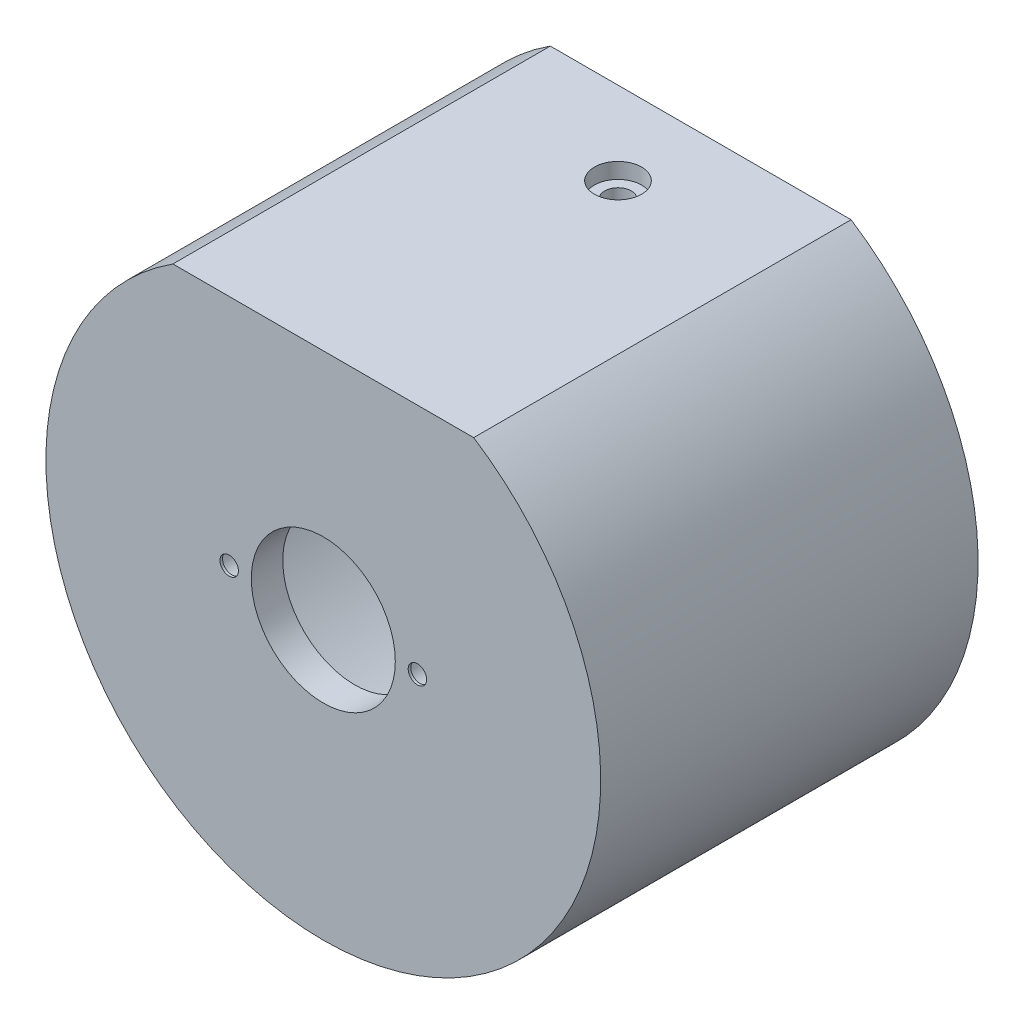
SolidWorks part; units mm, degrees
material "Acrylic (Medium-high impact)"
ref_plane "Front Plane" through (0, 0, 0) normal (0, 0, 1) x (1, 0, 0)
ref_plane "Top Plane" through (0, 0, 0) normal (0, 1, 0) x (1, 0, 0)
ref_plane "Right Plane" through (0, 0, 0) normal (1, 0, 0) x (0, 0, -1)
sketch "Sketch1" plane through (0, 0, 0) normal (0, 0, 1) x (1, 0, 0)
  line L0 (14.3753, 20.8636) -> (-14.3753, 20.8636)
  line L1 (14.1764, 20.2286) -> (-14.1764, 20.2286) construction
  line L2 (15.1825, 23.5306) -> (-15.1825, 23.5306)
  arc A0 (-14.3753, 20.8636) -> (14.3753, 20.8636) centre (0, 0) ccw
  arc A1 (-15.1825, 23.5306) -> (15.1825, 23.5306) centre (0, 0) ccw
  arc A2 (-14.1764, 20.2286) -> (14.1764, 20.2286) centre (0, 0) ccw construction
  dimension "D1" = 50.673
  dimension "D2" = 0.635
  dimension "D3" = 0.635
  dimension "D4" = 2.667
  dimension "D5" = 2.667
extrude "Boss-Extrude1" add sketch "Sketch1" along normal blind 38.1
sketch "Sketch10" plane through (0, 0, 38.1) normal (0, 0, 1) x (1, 0, 0)
  line L0 (15.1825, 23.5306) -> (-15.1825, 23.5306) construction
  line L1 (15.1825, 23.5306) -> (-15.1825, 23.5306)
  arc A0 (-15.1825, 23.5306) -> (15.1825, 23.5306) centre (0, 0) ccw
  circle A1 centre (0, 0) radius 28.0035 construction
extrude "Boss-Extrude2" add sketch "Sketch10" against normal blind 3.175
ref_plane "Plane1" through (0, 0, 10.2108) normal (0, 0, -1) x (-1, 0, 0)
sketch "Sketch11" plane through (0, 0, 10.2108) normal (0, 0, -1) x (-1, 0, 0)
  line L0 (0, 0) -> (0, 23.5306) construction
  line L1 (0, 0) -> (-14.0017, -24.2517) construction
  line L2 (0, 0) -> (28.0035, 0) construction
  line L3 (-15.1825, 23.5306) -> (15.1825, 23.5306) construction
  circle A0 centre (0, 0) radius 28.0035 construction
  dimension "D1" = 150
  dimension "D2" = 120
ref_plane "Plane2" through (-28.0035, 0, 10.2108) normal (-1, 0, 0) x (0, 0, -1)
ref_plane "Plane3" through (14.0017, -24.2517, 10.2108) normal (0.5, -0.866, 0) x (0, 0, 1)
ref_plane "Plane4" through (-28.0035, 0, 10.2108) normal (-1, 0, 0) x (0, 0, 1)
hole_wizard "CBORE for #2 Pan Head Machine Screw1" positions "Sketch15" profile "Sketch14" counterbore size "#2" standard "ANSI Inch" end condition up to next
sketch "Sketch15" plane through (-7.7474, 23.5306, 10.2108) normal (0, -1, 0) x (0, 0, -1)
  point P0 (1.8613, 7.7474)
sketch "Sketch14" plane through (0, 23.5306, 8.3495) normal (1, 0, 0) x (0, 0, 1)
  line L0 (0, 0) -> (0, 2.667)
  line L1 (0, 2.667) -> (1.3525, 2.667)
  line L3 (1.3525, 2.667) -> (1.3525, 1.5748)
  line L4 (1.3525, 1.5748) -> (2.3812, 1.5748)
  line L5 (2.3812, 1.5748) -> (2.3812, 0)
  line L7 (2.3812, 0) -> (0, 0)
  line L11 (0, -6.35) -> (0, 107.95) construction
  dimension "Thru Hole Dia." = 2.7051
  dimension "Thru Hole Depth" = 2.667
  dimension "C'Bore Dia." = 4.7625
  dimension "C'Bore Depth" = 1.5748
hole_wizard "CBORE for #2 Pan Head Machine Screw2" positions "Sketch17" profile "Sketch16" counterbore size "#2" standard "ANSI Inch" end condition up to next
sketch "Sketch17" plane through (14.0017, -24.2517, 10.2108) normal (0.5, -0.866, 0) x (0, 0, 1)
  point P0 (0, 0)
sketch "Sketch16" plane through (14.0017, -24.2517, 10.2108) normal (0, 0, 1) x (0.866, 0.5, 0)
  line L0 (0, 0) -> (0, 2.667)
  line L1 (0, 2.667) -> (1.3526, 2.667)
  line L3 (1.3526, 2.667) -> (1.3526, 1.5748)
  line L4 (1.3526, 1.5748) -> (2.3812, 1.5748)
  line L5 (2.3812, 1.5748) -> (2.3812, 0)
  line L7 (2.3812, 0) -> (0, 0)
  line L11 (0, -6.35) -> (0, 107.95) construction
  dimension "Thru Hole Dia." = 2.7051
  dimension "Thru Hole Depth" = 2.667
  dimension "C'Bore Dia." = 4.7625
  dimension "C'Bore Depth" = 1.5748
hole_wizard "CBORE for #2 Pan Head Machine Screw3" positions "Sketch19" profile "Sketch18" counterbore size "#2" standard "ANSI Inch" end condition up to next
sketch "Sketch19" plane through (-28.0035, 0, 10.2108) normal (-1, 0, 0) x (0, 0, 1)
  point P0 (0, 0)
sketch "Sketch18" plane through (-28.0035, 0, 10.2108) normal (0, 1, 0) x (0, 0, 1)
  line L0 (0, 0) -> (0, 2.667)
  line L1 (0, 2.667) -> (1.3526, 2.667)
  line L3 (1.3526, 2.667) -> (1.3526, 1.5748)
  line L4 (1.3526, 1.5748) -> (2.3812, 1.5748)
  line L5 (2.3812, 1.5748) -> (2.3812, 0)
  line L7 (2.3812, 0) -> (0, 0)
  line L11 (0, -6.35) -> (0, 107.95) construction
  dimension "Thru Hole Dia." = 2.7051
  dimension "Thru Hole Depth" = 2.667
  dimension "C'Bore Dia." = 4.7625
  dimension "C'Bore Depth" = 1.5748
sketch "Sketch20" plane through (0, 0, 38.1) normal (0, 0, 1) x (1, 0, 0)
  circle A0 centre (0, 0) radius 7.27
  circle A1 centre (0, 0) radius 6 construction
  dimension "D1" = 1.27
extrude "Cut-Extrude1" cut sketch "Sketch20" against normal up to next
hole_wizard "Hole1" positions "Sketch21" profile "Sketch22" legacy
sketch "Sketch21" plane through (0, 0, 34.925) normal (0, 0, -1) x (-1, 0, 0)
  point P0 (-9.5, 0)
  point P3 (9.5, 0)
sketch "Sketch22" plane through (9.5, 0, 34.925) normal (1, 0, 0) x (0, 1, 0)
  line L0 (0, 0) -> (0, 2.921)
  line L1 (0, 2.921) -> (1.4986, 2.921)
  line L2 (1.4986, 2.921) -> (1.6383, 0)
  line L3 (1.6383, 0) -> (0, 0)
  line L4 (0, 110) -> (0, -10) construction
  dimension "Minor Diameter" = 2.9972
  dimension "Depth" = 2.921
  dimension "Major Diameter" = 3.2766
hole_wizard "#0 Clearance Hole1" positions "Sketch23" profile "Sketch24" hole size "#0" standard "ANSI Inch" end condition up to next
sketch "Sketch23" plane through (0, 0, 34.925) normal (0, 0, -1) x (-1, 0, 0)
  point P0 (-9.5, 0)
  point P3 (9.5, 0)
sketch "Sketch24" plane through (9.5, 0, 34.925) normal (1, 0, 0) x (0, 1, 0)
  line L0 (0, 0) -> (0, 3.175)
  line L1 (0, 3.175) -> (0.9271, 3.175)
  line L2 (0.9271, 3.175) -> (0.9271, 0)
  line L5 (0.9271, 0) -> (0, 0)
  line L11 (0, -6.35) -> (0, 107.95) construction
  dimension "Thru Hole Dia." = 1.8542
  dimension "Thru Hole Depth" = 3.175
chamfer "Chamfer1" distance 1.27 angle 45 2 edges at (0, -25.3365, 0) (0, 20.8636, 0)
equation "\"D3@Sketch1\"=\"D2@Sketch1\""
equation "\"D5@Sketch1\"=\"D4@Sketch1\""
